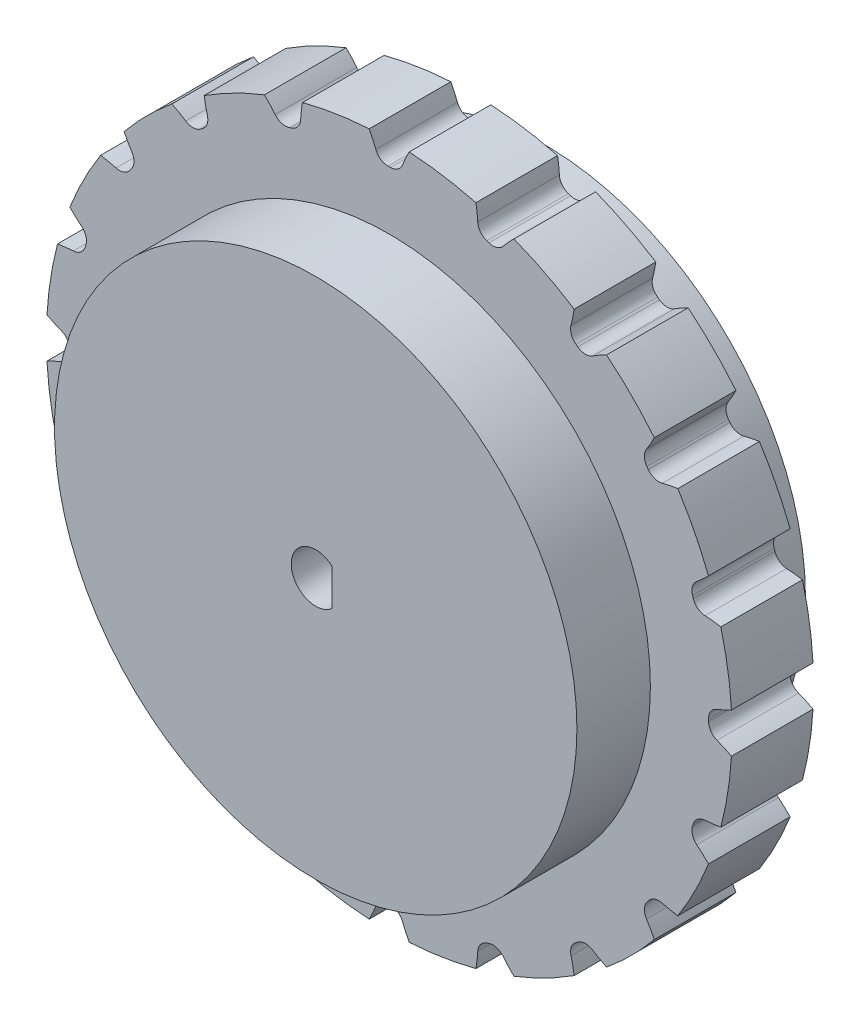
SolidWorks part; units mm, degrees
note: The reader was unsure of these and kept them because the rebuilt part matched: shared geometry of "草图1<3>", "草图7<3>", "草图6<3>", "草图6<4>", "草图8<3>".
ref_plane "前视基准面" through (0, 0, 0) normal (0, 0, 1) x (1, 0, 0)
ref_plane "上视基准面" through (0, 0, 0) normal (0, 1, 0) x (1, 0, 0)
ref_plane "右视基准面" through (0, 0, 0) normal (1, 0, 0) x (0, 0, -1)
other "Configuration Table"
sketch "草图1" plane through (0, 0, 0) normal (0, 0, 1) x (1, 0, 0)
  line L0 (0, 0) -> (20, 0) construction
  line L1 (0, 0) -> (19.9846, 0.7852) construction
  line L2 (0, 0) -> (18.7871, 0.504)
  line L3 (19.9846, 0.7852) -> (19.9846, -0.7852) construction
  line L4 (0, 0) -> (18.7871, -0.504)
  circle A0 centre (0, 0) radius 21
  circle A1 centre (0, 0) radius 20 construction
  circle A2 centre (0, 0) radius 18.75
  circle A3 centre (0, 0) radius 18.7939 construction
  circle A4 centre (0, 0) radius 0.25
  spline S0 degree 4 poles (18.7871, 0.504) (18.8228, 0.5049) (18.8942, 0.5091) (19.0362, 0.526) (19.3039, 0.5749) (19.6575, 0.6674) (20.1411, 0.8343) (20.7106, 1.084) (21.5687, 1.5407) (22.6879, 2.3053) (24.1076, 3.5604) (25.6701, 5.4273) (27.074, 7.7033) (28.2337, 10.3408) (29.058, 13.0999) (29.5655, 15.9335) (29.7841, 18.9458) (29.6646, 22.6841) (28.9514, 27.0937) (27.3833, 32.0436) (24.8126, 37.2063) (21.9386, 41.3515) (19.0952, 44.5994) (16.5034, 47.0888) (14.3082, 48.9453) (12.0035, 50.6631) (9.5988, 52.2393) (6.4845, 54.0296) (2.5878, 55.887) (-2.1371, 57.6247) (-6.6801, 58.7597) (-10.216, 59.3593) (-12.7243, 59.6531) (-14.1274, 59.7848) (-15.4932, 59.8733) (-16.5648, 59.9257) (-17.6976, 59.9533) (-18.2939, 59.9614) (-19.0193, 59.9628) (-19.5987, 59.9579) (-20.1711, 59.9472) (-20.7557, 59.9311) (-21.4768, 59.9038) (-22.3471, 59.8599) (-23.3581, 59.7924) (-24.514, 59.6932) (-25.6664, 59.5721) (-26.5298, 59.465) (-27.1038, 59.3863) (-27.3908, 59.3452) knots 0 0 0 0 0 0.001401 0.002802 0.005604 0.010661 0.015718 0.022839 0.02996 0.048734 0.068727 0.096889 0.125051 0.153212 0.181374 0.209535 0.237696 0.271429 0.327752 0.384075 0.440398 0.496721 0.524883 0.553044 0.581206 0.609367 0.637529 0.66569 0.722013 0.778336 0.834659 0.84874 0.86282 0.876901 0.890982 0.900036 0.909091 0.914773 0.920455 0.926136 0.931818 0.9375 0.943182 0.954545 0.965909 0.977273 0.988636 1 1 1 1 1 construction
  spline S1 degree 4 poles (18.7871, 0.504) (18.8228, 0.5049) (18.8942, 0.5091) (19.0362, 0.526) (19.3039, 0.5749) (19.6575, 0.6674) (20.1411, 0.8343) (20.7106, 1.084) (21.5687, 1.5407) (22.6879, 2.3053) (24.1076, 3.5604) (25.6701, 5.4273) (27.074, 7.7033) (28.2337, 10.3408) (29.058, 13.0999) (29.5655, 15.9335) (29.7841, 18.9458) (29.6646, 22.6841) (28.9514, 27.0937) (27.3833, 32.0436) (24.8126, 37.2063) (21.9386, 41.3515) (19.0952, 44.5994) (16.5034, 47.0888) (14.3082, 48.9453) (12.0035, 50.6631) (9.5988, 52.2393) (6.4845, 54.0296) (2.5878, 55.887) (-2.1371, 57.6247) (-6.6801, 58.7597) (-10.216, 59.3593) (-12.7243, 59.6531) (-14.1274, 59.7848) (-15.4932, 59.8733) (-16.5648, 59.9257) (-17.5276, 59.9492) (-17.9359, 59.9561) (-18.1458, 59.9584) knots 0 0 0 0 0 0.001401 0.002802 0.005604 0.010661 0.015718 0.022839 0.02996 0.048734 0.068727 0.096889 0.125051 0.153212 0.181374 0.209535 0.237696 0.271429 0.327752 0.384075 0.440398 0.496721 0.524883 0.553044 0.581206 0.609367 0.637529 0.66569 0.722013 0.778336 0.834659 0.84874 0.86282 0.876901 0.890982 0.900036 0.909091 0.909091 0.909091 0.909091 0.909091
  spline S2 degree 4 poles (18.7871, -0.504) (18.8228, -0.5049) (18.8942, -0.5091) (19.0362, -0.526) (19.3039, -0.5749) (19.6575, -0.6674) (20.1411, -0.8343) (20.7106, -1.084) (21.5687, -1.5407) (22.6879, -2.3053) (24.1076, -3.5604) (25.6701, -5.4273) (27.074, -7.7033) (28.2337, -10.3408) (29.058, -13.0999) (29.5655, -15.9335) (29.7841, -18.9458) (29.6646, -22.6841) (28.9514, -27.0937) (27.3833, -32.0436) (24.8126, -37.2063) (21.9386, -41.3515) (19.0952, -44.5994) (16.5034, -47.0888) (14.3082, -48.9453) (12.0035, -50.6631) (9.5988, -52.2393) (6.4845, -54.0296) (2.5878, -55.887) (-2.1371, -57.6247) (-6.6801, -58.7597) (-10.216, -59.3593) (-12.7243, -59.6531) (-14.1274, -59.7848) (-15.4932, -59.8733) (-16.5648, -59.9257) (-17.6976, -59.9533) (-18.2939, -59.9614) (-19.0193, -59.9628) (-19.5987, -59.9579) (-20.1711, -59.9472) (-20.7557, -59.9311) (-21.4768, -59.9038) (-22.3471, -59.8599) (-23.3581, -59.7924) (-24.514, -59.6932) (-25.6664, -59.5721) (-26.5298, -59.465) (-27.1038, -59.3863) (-27.3908, -59.3452) knots 0 0 0 0 0 0.001401 0.002802 0.005604 0.010661 0.015718 0.022839 0.02996 0.048734 0.068727 0.096889 0.125051 0.153212 0.181374 0.209535 0.237696 0.271429 0.327752 0.384075 0.440398 0.496721 0.524883 0.553044 0.581206 0.609367 0.637529 0.66569 0.722013 0.778336 0.834659 0.84874 0.86282 0.876901 0.890982 0.900036 0.909091 0.914773 0.920455 0.926136 0.931818 0.9375 0.943182 0.954545 0.965909 0.977273 0.988636 1 1 1 1 1 construction
  spline S3 degree 4 poles (18.7871, -0.504) (18.8228, -0.5049) (18.8942, -0.5091) (19.0362, -0.526) (19.3039, -0.5749) (19.6575, -0.6674) (20.1411, -0.8343) (20.7106, -1.084) (21.5687, -1.5407) (22.6879, -2.3053) (24.1076, -3.5604) (25.6701, -5.4273) (27.074, -7.7033) (28.2337, -10.3408) (29.058, -13.0999) (29.5655, -15.9335) (29.7841, -18.9458) (29.6646, -22.6841) (28.9514, -27.0937) (27.3833, -32.0436) (24.8126, -37.2063) (21.9386, -41.3515) (19.0952, -44.5994) (16.5034, -47.0888) (14.3082, -48.9453) (12.0035, -50.6631) (9.5988, -52.2393) (6.4845, -54.0296) (2.5878, -55.887) (-2.1371, -57.6247) (-6.6801, -58.7597) (-10.216, -59.3593) (-12.7243, -59.6531) (-14.1274, -59.7848) (-15.4932, -59.8733) (-16.5648, -59.9257) (-17.5276, -59.9492) (-17.9359, -59.9561) (-18.1458, -59.9584) knots 0 0 0 0 0 0.001401 0.002802 0.005604 0.010661 0.015718 0.022839 0.02996 0.048734 0.068727 0.096889 0.125051 0.153212 0.181374 0.209535 0.237696 0.271429 0.327752 0.384075 0.440398 0.496721 0.524883 0.553044 0.581206 0.609367 0.637529 0.66569 0.722013 0.778336 0.834659 0.84874 0.86282 0.876901 0.890982 0.900036 0.909091 0.909091 0.909091 0.909091 0.909091
  point P15 (19.9846, 0)
  dimension "齿顶圆直径" = 42
  dimension "分度圆直径" = 40
  dimension "齿根圆直径" = 37.5
  dimension "基圆直径" = 37.5877
  dimension "内孔直径" = 0.5
  dimension "渐近线镜像线夹角" = 2.25
extrude "凸台-拉伸1" add sketch "草图1" along normal blind 5 contours A0 | A4
extrude "切除-拉伸1" cut sketch "草图1<3>" along normal through all contours A2 S3 A0 S1
sketch "草图1<3>" plane through (0, 0, 0) normal (0, 0, 1) x (1, 0, 0) same geometry as "草图1"
sketch "草图3" plane through (5.4955, 0, 0) normal (0, 0, -1) x (-1, 0, 0)
  line L0 (25.5591, 0) -> (5.4955, 0)
  line L1 (21.7273, -11.7931) -> (5.4955, 0)
  line L2 (25.5591, 0) -> (21.7273, -11.7931)
  circle A1 centre (5.4955, 0) radius 20.0636
  arc A2 (-13.2478, 0.5028) -> (-13.2478, -0.5028) centre (5.4955, 0) ccw construction
  arc A3 (-15.4688, -1.2244) -> (-15.4688, 1.2244) centre (5.4955, 0) ccw construction
  point P3 (24.2455, 0)
  dimension "D1" = 36
  dimension "D2" = 12.4
  dimension "D3" = 0.9364
sketch "草图4" plane through (0, 0, 0) normal (0, 0, 1) x (1, 0, 0)
  circle A0 centre (0, 0) radius 21
  dimension "D1" = 42
extrude "凸台-拉伸2" add sketch "草图4" along normal through all
sketch "草图5" plane through (0, 0, 0) normal (0, 0, 1) x (1, 0, 0)
  circle A1 centre (0, 0) radius 20.0636 construction
  circle A2 centre (0, 0) radius 21
  circle A3 centre (0, 0) radius 20.0636
  circle A6 centre (0, 0) radius 19.5636
  spline S0 degree 4 poles (-33.188, -3997.5485) (11.8279, 80.4576) (14.0745, 2.1662) (16.8154, 0.1203) (19.3039, 0.5749) (19.6575, 0.6674) (20.1411, 0.8343) (20.7106, 1.084) (21.5687, 1.5407) (22.6879, 2.3053) (24.1076, 3.5604) (25.6701, 5.4273) (27.074, 7.7033) (28.2337, 10.3408) (29.058, 13.0999) (29.5655, 15.9335) (29.7841, 18.9458) (29.6646, 22.6841) (28.9514, 27.0937) (27.3833, 32.0436) (24.8126, 37.2063) (21.9386, 41.3515) (19.0952, 44.5994) (16.5034, 47.0888) (14.3082, 48.9453) (12.0035, 50.6631) (9.5988, 52.2393) (6.4845, 54.0296) (2.5878, 55.887) (-2.1371, 57.6247) (-6.6801, 58.7597) (-10.216, 59.3593) (-12.7243, 59.6531) (-14.1274, 59.7848) (-15.4932, 59.8733) (-19.7499, 60.0813) (-29.7213, 59.914) (84.4, 58.0544) (-4016.2635, 102.528) knots -0.08846 -0.08846 -0.08846 -0.08846 -0.08846 0.001401 0.002802 0.005604 0.010661 0.015718 0.022839 0.02996 0.048734 0.068727 0.096889 0.125051 0.153212 0.181374 0.209535 0.237696 0.271429 0.327752 0.384075 0.440398 0.496721 0.524883 0.553044 0.581206 0.609367 0.637529 0.66569 0.722013 0.778336 0.834659 0.84874 0.86282 0.876901 0.890982 0.900036 1.046617 1.046617 1.046617 1.046617 1.046617 only from (18.7871, 0.504) to (-18.1458, 59.9584) construction
  spline S1 degree 4 poles (18.7871, 0.504) (18.8228, 0.5049) (18.8942, 0.5091) (19.0362, 0.526) (19.3039, 0.5749) (19.6575, 0.6674) (20.1411, 0.8343) (20.7106, 1.084) (21.5687, 1.5407) (22.6879, 2.3053) (24.1076, 3.5604) (25.6701, 5.4273) (27.074, 7.7033) (28.2337, 10.3408) (29.058, 13.0999) (29.5655, 15.9335) (29.7841, 18.9458) (29.6646, 22.6841) (28.9514, 27.0937) (27.3833, 32.0436) (24.8126, 37.2063) (21.9386, 41.3515) (19.0952, 44.5994) (16.5034, 47.0888) (14.3082, 48.9453) (12.0035, 50.6631) (9.5988, 52.2393) (6.4845, 54.0296) (2.5878, 55.887) (-2.1371, 57.6247) (-6.6801, 58.7597) (-10.216, 59.3593) (-12.7243, 59.6531) (-14.1274, 59.7848) (-15.4932, 59.8733) (-16.5648, 59.9257) (-17.5276, 59.9492) (-17.9359, 59.9561) (-18.1458, 59.9584) knots 0 0 0 0 0 0.001401 0.002802 0.005604 0.010661 0.015718 0.022839 0.02996 0.048734 0.068727 0.096889 0.125051 0.153212 0.181374 0.209535 0.237696 0.271429 0.327752 0.384075 0.440398 0.496721 0.524883 0.553044 0.581206 0.609367 0.637529 0.66569 0.722013 0.778336 0.834659 0.84874 0.86282 0.876901 0.890982 0.900036 0.909091 0.909091 0.909091 0.909091 0.909091
  spline S2 degree 4 poles (18.7871, 0.504) (18.8228, 0.5049) (18.8942, 0.5091) (19.0362, 0.526) (19.3039, 0.5749) (19.6575, 0.6674) (20.1411, 0.8343) (20.7106, 1.084) (21.5687, 1.5407) (22.6879, 2.3053) (24.1076, 3.5604) (25.6701, 5.4273) (27.074, 7.7033) (28.2337, 10.3408) (29.058, 13.0999) (29.5655, 15.9335) (29.7841, 18.9458) (29.6646, 22.6841) (28.9514, 27.0937) (27.3833, 32.0436) (24.8126, 37.2063) (21.9386, 41.3515) (19.0952, 44.5994) (16.5034, 47.0888) (14.3082, 48.9453) (12.0035, 50.6631) (9.5988, 52.2393) (6.4845, 54.0296) (2.5878, 55.887) (-2.1371, 57.6247) (-6.6801, 58.7597) (-10.216, 59.3593) (-12.7243, 59.6531) (-14.1274, 59.7848) (-15.4932, 59.8733) (-16.5648, 59.9257) (-17.5276, 59.9492) (-17.9359, 59.9561) (-18.1458, 59.9584) knots 0 0 0 0 0 0.001401 0.002802 0.005604 0.010661 0.015718 0.022839 0.02996 0.048734 0.068727 0.096889 0.125051 0.153212 0.181374 0.209535 0.237696 0.271429 0.327752 0.384075 0.440398 0.496721 0.524883 0.553044 0.581206 0.609367 0.637529 0.66569 0.722013 0.778336 0.834659 0.84874 0.86282 0.876901 0.890982 0.900036 0.909091 0.909091 0.909091 0.909091 0.909091
  spline S3 degree 4 poles (18.7871, -0.504) (18.8228, -0.5049) (18.8942, -0.5091) (19.0362, -0.526) (19.3039, -0.5749) (19.6575, -0.6674) (20.1411, -0.8343) (20.7106, -1.084) (21.5687, -1.5407) (22.6879, -2.3053) (24.1076, -3.5604) (25.6701, -5.4273) (27.074, -7.7033) (28.2337, -10.3408) (29.058, -13.0999) (29.5655, -15.9335) (29.7841, -18.9458) (29.6646, -22.6841) (28.9514, -27.0937) (27.3833, -32.0436) (24.8126, -37.2063) (21.9386, -41.3515) (19.0952, -44.5994) (16.5034, -47.0888) (14.3082, -48.9453) (12.0035, -50.6631) (9.5988, -52.2393) (6.4845, -54.0296) (2.5878, -55.887) (-2.1371, -57.6247) (-6.6801, -58.7597) (-10.216, -59.3593) (-12.7243, -59.6531) (-14.1274, -59.7848) (-15.4932, -59.8733) (-16.5648, -59.9257) (-17.6976, -59.9533) (-18.2939, -59.9614) (-19.0193, -59.9628) (-19.5987, -59.9579) (-20.1711, -59.9472) (-20.7557, -59.9311) (-21.4768, -59.9038) (-22.3471, -59.8599) (-23.3581, -59.7924) (-24.514, -59.6932) (-25.6664, -59.5721) (-26.5298, -59.465) (-27.1038, -59.3863) (-27.3908, -59.3452) knots 0 0 0 0 0 0.001401 0.002802 0.005604 0.010661 0.015718 0.022839 0.02996 0.048734 0.068727 0.096889 0.125051 0.153212 0.181374 0.209535 0.237696 0.271429 0.327752 0.384075 0.440398 0.496721 0.524883 0.553044 0.581206 0.609367 0.637529 0.66569 0.722013 0.778336 0.834659 0.84874 0.86282 0.876901 0.890982 0.900036 0.909091 0.914773 0.920455 0.926136 0.931818 0.9375 0.943182 0.954545 0.965909 0.977273 0.988636 1 1 1 1 1 construction
  spline S4 degree 4 poles (18.7871, -0.504) (18.8228, -0.5049) (18.8942, -0.5091) (19.0362, -0.526) (19.3039, -0.5749) (19.6575, -0.6674) (20.1411, -0.8343) (20.7106, -1.084) (21.5687, -1.5407) (22.6879, -2.3053) (24.1076, -3.5604) (25.6701, -5.4273) (27.074, -7.7033) (28.2337, -10.3408) (29.058, -13.0999) (29.5655, -15.9335) (29.7841, -18.9458) (29.6646, -22.6841) (28.9514, -27.0937) (27.3833, -32.0436) (24.8126, -37.2063) (21.9386, -41.3515) (19.0952, -44.5994) (16.5034, -47.0888) (14.3082, -48.9453) (12.0035, -50.6631) (9.5988, -52.2393) (6.4845, -54.0296) (2.5878, -55.887) (-2.1371, -57.6247) (-6.6801, -58.7597) (-10.216, -59.3593) (-12.7243, -59.6531) (-14.1274, -59.7848) (-15.4932, -59.8733) (-16.5648, -59.9257) (-17.5276, -59.9492) (-17.9359, -59.9561) (-18.1458, -59.9584) knots 0 0 0 0 0 0.001401 0.002802 0.005604 0.010661 0.015718 0.022839 0.02996 0.048734 0.068727 0.096889 0.125051 0.153212 0.181374 0.209535 0.237696 0.271429 0.327752 0.384075 0.440398 0.496721 0.524883 0.553044 0.581206 0.609367 0.637529 0.66569 0.722013 0.778336 0.834659 0.84874 0.86282 0.876901 0.890982 0.900036 0.909091 0.909091 0.909091 0.909091 0.909091
  dimension "D2" = 42
  dimension "D1" = 0.5
extrude "切除-拉伸2" cut sketch "草图5" against normal through all and the other way through all contours A3 S4 A2 S1 | A6 S4 A3 S1
fillet "圆角1" radius 0.8 2 edges at (19.553, -0.6442, 2.5) (19.553, 0.6442, 2.5)
pattern_circular "阵列(圆周)1" count 20 over 360 about axis through (0, 0, 5) along (0, 0, 1) of "圆角1", "切除-拉伸2"
sketch "草图7" plane through (0, 0, 0) normal (0, 0, 1) x (1, 0, 0)
  circle A0 centre (0, 0) radius 16
  dimension "D1" = 32
extrude "凸台-拉伸3" add sketch "草图7" along normal blind 4.5 from surface at 5 contours A0 starting at face at (0, 0, 5)
extrude "凸台-拉伸4" add sketch "草图7<3>" against normal blind 4.5 from surface at 0 starting at face at (0, 0, 0)
sketch "草图7<3>" plane through (0, 0, 0) normal (0, 0, 1) x (1, 0, 0) same geometry as "草图7"
sketch "草图6" plane through (0, 0, 0) normal (0, 0, 1) x (1, 0, 0)
  circle A0 centre (0, 0) radius 3.1
  circle A1 centre (0, 0) radius 1.75
  dimension "D1" = 6.2
  dimension "D2" = 3.5
extrude "切除-拉伸3" cut sketch "草图6" along normal through all both and the other way through all contours A1
extrude "切除-拉伸4" cut sketch "草图6<3>" along normal blind 2.6 from surface at -4.5 contours A0 starting at face at (1.75, 0, -4.5)
sketch "草图6<3>" plane through (0, 0, 0) normal (0, 0, 1) x (1, 0, 0) same geometry as "草图6"
extrude "切除-拉伸5" cut sketch "草图6<4>" against normal blind 2.6 from surface at 9.5 starting at face at (1.75, 0, 9.5)
sketch "草图6<4>" plane through (0, 0, 0) normal (0, 0, 1) x (1, 0, 0) same geometry as "草图6"
sketch "草图8" plane through (0, 0, 0) normal (0, 0, 1) x (1, 0, 0)
  line L0 (1, 1.118) -> (1, -1.118)
  circle A0 centre (0, 0) radius 4
  circle A1 centre (0, 0) radius 1.5
  dimension "D1" = 3
  dimension "D3" = 8
  dimension "D2" = 1
extrude "凸台-拉伸5" add sketch "草图8" along normal through all and the other way through all contours A0
extrude "切除-拉伸6" cut sketch "草图8<3>" against normal through all both and the other way through all contours L0 A1
sketch "草图8<3>" plane through (0, 0, 0) normal (0, 0, 1) x (1, 0, 0) same geometry as "草图8"
equation "\"m\"= 1'模数"
equation "\"z\"= 40'齿数"
equation "\"a\"= 20度'压力角"
equation "\"d\"= \"m\" * \"z\"'分度圆直径"
equation "\"da\"= ( \"z\" + 2 ) * \"m\"'齿顶圆直径"
equation "\"df\"= ( \"z\" - 2.5 ) * \"m\"'齿根圆直径"
equation "\"s\"= 0.5 * PI * \"m\"'分度圆齿厚"
equation "\"r\"= 0.38 * \"m\"'齿根圆角"
equation "\"B\"= 0.3 * \"d\"'齿厚"
equation "\"db\"= \"m\" * \"z\" * cos ( \"a\" )'基圆直径"
equation "\"rb\"= \"db\" / 2'基圆半径"
equation "\"齿顶圆直径@草图1\"= \"da\""
equation "\"分度圆直径@草图1\"= \"d\""
equation "\"齿根圆直径@草图1\"= \"df\""
equation "\"基圆直径@草图1\"= \"db\""
equation "\"渐近线镜像线夹角@草图1\"= 360 / 4 / \"z\""
equation "\"h\"= 5'齿轮厚度"
equation "\"ir\"= 0.5'内孔直径"
equation "\"内孔直径@草图1\"= \"ir\""
equation "\"齿轮厚@凸台-拉伸1\"= \"h\""
equation "\"D1@草图3\"=360  * 4  / \"z\""
equation "\"D2@草图5\"=\"da\""
equation "\"D1@草图4\"=\"da\""
